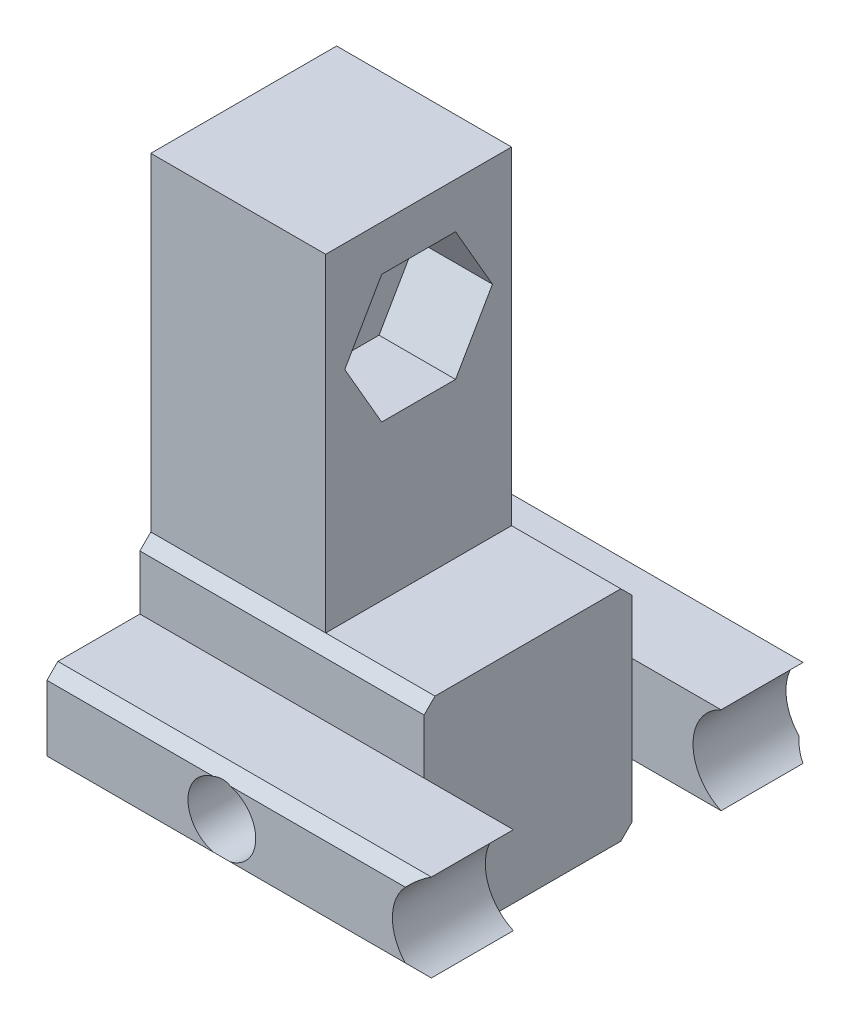
SolidWorks part; units mm, degrees
ref_plane "Front Plane" through (0, 0, 0) normal (0, 0, 1) x (1, 0, 0)
ref_plane "Top Plane" through (0, 0, 0) normal (0, 1, 0) x (1, 0, 0)
ref_plane "Right Plane" through (0, 0, 0) normal (1, 0, 0) x (0, 0, -1)
sketch "Sketch1" plane through (0, 0, 0) normal (0, 0, 1) x (1, 0, 0)
  line L0 (-0.9165, 2) -> (-50, 2)
  line L1 (-50, 2) -> (-50, -2)
  line L3 (-50, -2) -> (-0.9165, -2)
  arc A0 (-0.9165, 2) -> (-0.9165, -2) centre (0, 0) ccw
  dimension "D2" = 4
  dimension "D1" = 2.2
  dimension "D3" = 2
  dimension "D4" = 50
extrude "Boss-Extrude1" add sketch "Sketch1" along normal blind 18
sketch "Sketch2" plane through (-50, 0, 0) normal (-1, 0, 0) x (0, 0, 1)
  line L1 (4.25, 5) -> (13.75, 5)
  line L2 (4.25, 5) -> (4.25, -5)
  line L3 (4.25, -5) -> (13.75, -5)
  line L4 (13.75, 5) -> (13.75, -5)
  line L6 (18, 2) -> (18, -2) construction
  line L7 (18, 2) -> (0, 2) construction
  point P4 (4.25, 0)
  point P7 (18, 0)
  point P8 (9, 5)
  point P11 (9, 2)
  dimension "D1" = 9.5
  dimension "D3" = 10
extrude "Boss-Extrude2" add sketch "Sketch2" against normal up to vertex (49.0835 mm away) up to point (-0.9165, 2, 0)
sketch "Sketch3" plane through (0, 2, 0) normal (0, 1, 0) x (1, 0, 0)
  line L1 (-0.9165, -4.25) -> (4.0835, -4.25)
  line L2 (-0.9165, -4.25) -> (-0.9165, -13.75)
  line L3 (-0.9165, -13.75) -> (4.0835, -13.75)
  line L4 (4.0835, -4.25) -> (4.0835, -13.75)
  dimension "D1" = 9.5
  dimension "D2" = 5
sketch "Sketch4" plane through (0, 0, 18) normal (0, 0, 1) x (1, 0, 0)
  line L0 (-0.9165, 2) -> (-50, 2) construction
  point P0 (-10, 0)
  dimension "D1" = 10
  dimension "D2" = 2
hole_wizard "M3 Clearance Hole1" positions "Sketch5" profile "Sketch6" hole size "M3" standard "DIN" end condition through all
sketch "Sketch5" plane through (0, 0, 18) normal (0, 0, 1) x (1, 0, 0)
  point P0 (-10, 0)
sketch "Sketch6" plane through (-10, 0, 18) normal (1, 0, 0) x (0, -1, 0)
  line L0 (0, 0) -> (0, 18)
  line L1 (0, 18) -> (1.55, 18)
  line L2 (1.55, 18) -> (1.55, 0)
  line L5 (1.55, 0) -> (0, 0)
  line L11 (0, -6.35) -> (0, 107.95) construction
  dimension "Thru Hole Dia." = 3.1
  dimension "Thru Hole Depth" = 18
sketch "Sketch7" plane through (-50, 0, 0) normal (-1, 0, 0) x (0, 0, 1)
  line L0 (0, 2) -> (0, -2)
  line L1 (0, -2) -> (4.25, -2)
  line L2 (4.25, -2) -> (4.25, -5)
  line L3 (4.25, -5) -> (13.75, -5)
  line L4 (13.75, -5) -> (13.75, -2)
  line L5 (13.75, -2) -> (18, -2)
  line L6 (18, -2) -> (18, 2)
  line L7 (18, 2) -> (13.75, 2)
  line L8 (13.75, 2) -> (13.75, 5)
  line L9 (13.75, 5) -> (4.25, 5)
  line L10 (4.25, 5) -> (4.25, 2)
  line L11 (4.25, 2) -> (0, 2)
extrude "Boss-Extrude3" add sketch "Sketch7" along normal blind 1.5
chamfer "Chamfer1" distance 0.5 angle 45 8 edges at (-26.2083, -5, 4.25) (-26.2083, -5, 13.75) (-26.2083, 5, 13.75) (-26.2083, 5, 4.25) (-26.2083, -2, 0) (-26.2083, 2, 0) (-26.2083, -2, 18) (-26.2083, 2, 18)
sketch "Sketch8" plane through (0, 5, 0) normal (0, 1, 0) x (1, 0, 0)
  line L0 (-51.5, -4.25) -> (-0.9165, -4.25) construction
  line L1 (0, -4.25) -> (-5, -4.25)
  line L2 (0, -4.25) -> (0, -13.75)
  line L3 (0, -13.75) -> (-5, -13.75)
  line L4 (-5, -4.25) -> (-5, -13.75)
  line L5 (-0.9165, -13.75) -> (-51.5, -13.75) construction
  dimension "D1" = 5
extrude "Cut-Extrude1" cut sketch "Sketch8" against normal through all
sketch "Sketch9" plane through (0, 5, 0) normal (0, 1, 0) x (1, 0, 0)
  line L0 (-5, -4.75) -> (-51.5, -4.75) construction
  line L1 (-10, -4.75) -> (-18, -4.75)
  line L2 (-10, -4.75) -> (-10, -13.25)
  line L3 (-10, -13.25) -> (-18, -13.25)
  line L4 (-18, -4.75) -> (-18, -13.25)
  line L5 (-51.5, -13.25) -> (-5, -13.25) construction
  line L6 (-5, -4.75) -> (-5, -13.25) construction
  line L8 (0, 0) -> (0, -18.6346) construction
  dimension "D1" = 5
  dimension "D2" = 18
extrude "Boss-Extrude4" add sketch "Sketch9" along normal blind 15
sketch "Sketch10" plane through (-18, 0, 0) normal (-1, 0, 0) x (0, 0, 1)
  line L1 (4.75, 5) -> (13.25, 5) construction
  line L2 (4.75, 20) -> (13.25, 20) construction
  circle A0 centre (9, 15) radius 1.7
  point P7 (9, 20)
  dimension "D1" = 3.4
  dimension "D2" = 10
extrude "Cut-Extrude2" cut sketch "Sketch10" against normal blind 10
sketch "Sketch11" plane through (-10, 0, 0) normal (1, 0, 0) x (0, 0, -1)
  line L0 (-13.25, 20) -> (-4.75, 20) construction
  line L1 (-5.6225, 15) -> (-7.3113, 17.925)
  line L2 (-7.3113, 17.925) -> (-10.6887, 17.925)
  line L3 (-10.6887, 17.925) -> (-12.3775, 15)
  line L4 (-12.3775, 15) -> (-10.6887, 12.075)
  line L5 (-10.6887, 12.075) -> (-7.3113, 12.075)
  line L6 (-7.3113, 12.075) -> (-5.6225, 15)
  circle A0 centre (-9, 15) radius 2.925 construction
  dimension "D1" = 5.85
extrude "Cut-Extrude3" cut sketch "Sketch11" against normal blind 3.5
sketch "Sketch12" plane through (-18, 0, 0) normal (-1, 0, 0) x (0, 0, 1)
  circle A0 centre (9, 15) radius 3.25
  dimension "D1" = 6.5
sketch "Sketch13" plane through (0, 20, 0) normal (0, 1, 0) x (1, 0, 0)
  line L0 (-18, -4.75) -> (-18, -13.25) construction
  line L1 (-51.5, 0) -> (-18, 0)
  line L2 (-51.5, 0) -> (-51.5, -18)
  line L3 (-51.5, -18) -> (-18, -18)
  line L4 (-18, 0) -> (-18, -18)
  line L5 (-10.3905, -18) -> (-51.5, -18) construction
  line L6 (-51.5, 0) -> (-10.3905, 0) construction
  line L7 (-51.5, -13.25) -> (-51.5, -4.75) construction
extrude "Cut-Extrude5" cut sketch "Sketch13" against normal through all
chamfer "Chamfer2" distance 0.5 angle 45 1 edges at (-18, 15, 10.7)
